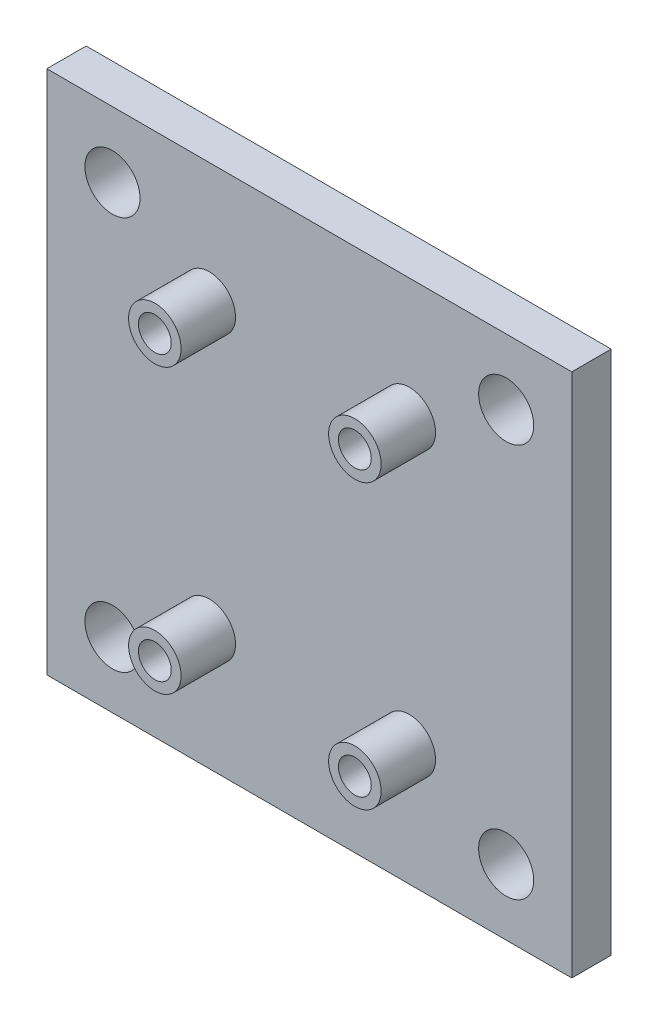
SolidWorks part; units mm, degrees
material "ABS"
ref_plane "前基準面" through (0, 0, 0) normal (0, 0, 1) x (1, 0, 0)
ref_plane "上基準面" through (0, 0, 0) normal (0, 1, 0) x (1, 0, 0)
ref_plane "右基準面" through (0, 0, 0) normal (1, 0, 0) x (0, 0, -1)
sketch "草圖1" plane through (0, 0, 0) normal (0, 0, 1) x (1, 0, 0)
  line L1 (-20, -20) -> (20, -20)
  line L2 (-20, -20) -> (-20, 20)
  line L3 (-20, 20) -> (20, 20)
  line L4 (20, -20) -> (20, 20)
  line L5 (-20, -20) -> (20, 20) construction
  line L6 (-20, 20) -> (20, -20) construction
  point P0 (0, 0)
  dimension "D1" = 40
  dimension "D2" = 40
extrude "填料-伸長1" add sketch "草圖1" along normal blind 3
sketch "草圖2" plane through (0, 0, 3) normal (0, 0, 1) x (1, 0, 0)
  line L0 (-20, 0) -> (20, 0) construction
  line L1 (-20, 20) -> (-20, -20) construction
  line L2 (20, -20) -> (20, 20) construction
  line L3 (0, 20) -> (0, -20) construction
  line L4 (20, 20) -> (-20, 20) construction
  line L5 (-20, -20) -> (20, -20) construction
  circle A0 centre (-7.62, 10.795) radius 2
  circle A1 centre (-7.62, -10.795) radius 2
  circle A2 centre (7.62, -10.795) radius 2
  circle A3 centre (7.62, 10.795) radius 2
  dimension "D1" = 4
  dimension "D2" = 7.62
  dimension "D3" = 10.795
extrude "填料-伸長2" add sketch "草圖2" along normal blind 4.15
sketch "草圖3" plane through (0, 0, 7.15) normal (0, 0, 1) x (1, 0, 0)
  line L0 (-20, 0) -> (20, 0) construction
  line L1 (0, 20) -> (0, -20) construction
  line L2 (20, 20) -> (-20, 20) construction
  line L3 (-20, -20) -> (20, -20) construction
  line L5 (20, -20) -> (20, 20) construction
  line L6 (-20, 20) -> (-20, -20) construction
  circle A0 centre (-7.62, 10.795) radius 1.25
  circle A1 centre (-7.62, -10.795) radius 1.25
  circle A2 centre (7.62, -10.795) radius 1.25
  circle A3 centre (7.62, 10.795) radius 1.25
  dimension "D1" = 2.5
sketch "草圖4" plane through (0, 0, 3) normal (0, 0, 1) x (1, 0, 0)
  line L0 (-20, 0) -> (20, 0) construction
  line L1 (-20, 20) -> (-20, -20) construction
  line L2 (20, -20) -> (20, 20) construction
  line L3 (0, 20) -> (0, -20) construction
  line L4 (20, 20) -> (-20, 20) construction
  line L5 (-20, -20) -> (20, -20) construction
  circle A0 centre (-15, 15) radius 2.1
  circle A1 centre (-15, -15) radius 2.1
  circle A2 centre (15, -15) radius 2.1
  circle A3 centre (15, 15) radius 2.1
  dimension "D1" = 4.2
  dimension "D2" = 15
  dimension "D3" = 15
extrude "除料-伸長1" cut sketch "草圖4" against normal through all
extrude "除料-伸長2" cut sketch "草圖3" against normal blind 4.15
